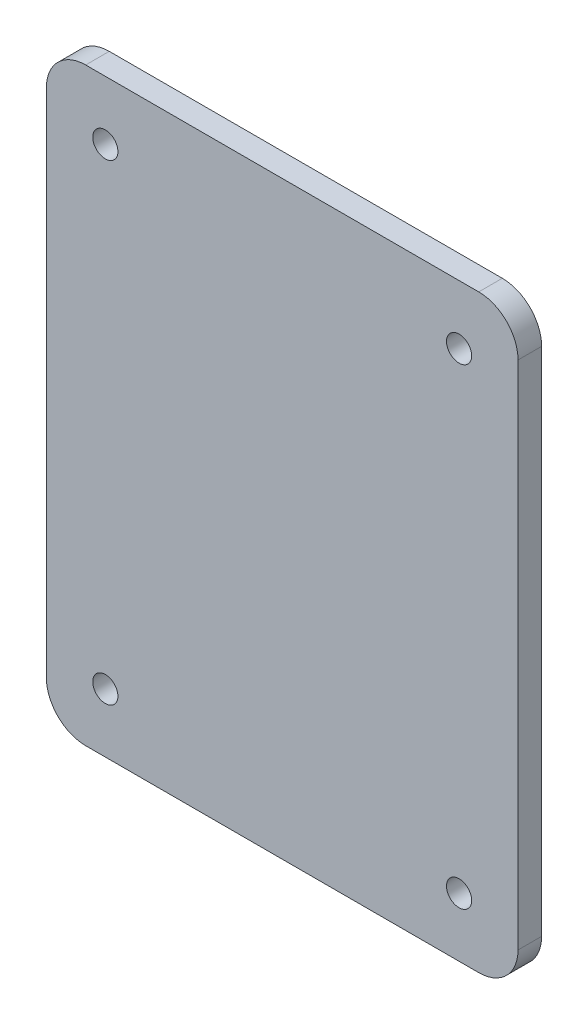
SolidWorks part; units mm, degrees
ref_plane "正面" through (0, 0, 0) normal (0, 0, 1) x (1, 0, 0)
ref_plane "平面" through (0, 0, 0) normal (0, 1, 0) x (1, 0, 0)
ref_plane "右側面" through (0, 0, 0) normal (1, 0, 0) x (0, 0, -1)
sketch "ｽｹｯﾁ2" plane through (0, 0, 0) normal (0, 0, 1) x (1, 0, 0)
  line L0 (0, -7.5) -> (60, -7.5) construction
  line L1 (0, 0) -> (60, 0)
  line L2 (0, 0) -> (0, -75)
  line L3 (0, -75) -> (60, -75)
  line L4 (60, 0) -> (60, -75)
  line L5 (0, -67.5) -> (60, -67.5) construction
  line L6 (7.5, -7.5) -> (7.5, -67.5) construction
  line L7 (52.5, -7.5) -> (52.5, -67.5) construction
  circle A0 centre (7.5, -7.5) radius 1.6
  circle A1 centre (52.5, -7.5) radius 1.6
  circle A2 centre (7.5, -67.5) radius 1.6
  circle A3 centre (52.5, -67.5) radius 1.6
  dimension "D4" = 3.2
  dimension "D5" = 7.5
  dimension "D6" = 7.5
  dimension "D7" = 60
  dimension "D1" = 7.5
  dimension "D2" = 60
  dimension "D8" = 7.5
extrude "ﾎﾞｽ - 押し出し1" add sketch "ｽｹｯﾁ2" along normal blind 3
fillet "ﾌｨﾚｯﾄ1" radius 5 4 edges at (0, -75, 1.5) (0, 0, 1.5) (60, -75, 1.5) (60, 0, 1.5)
